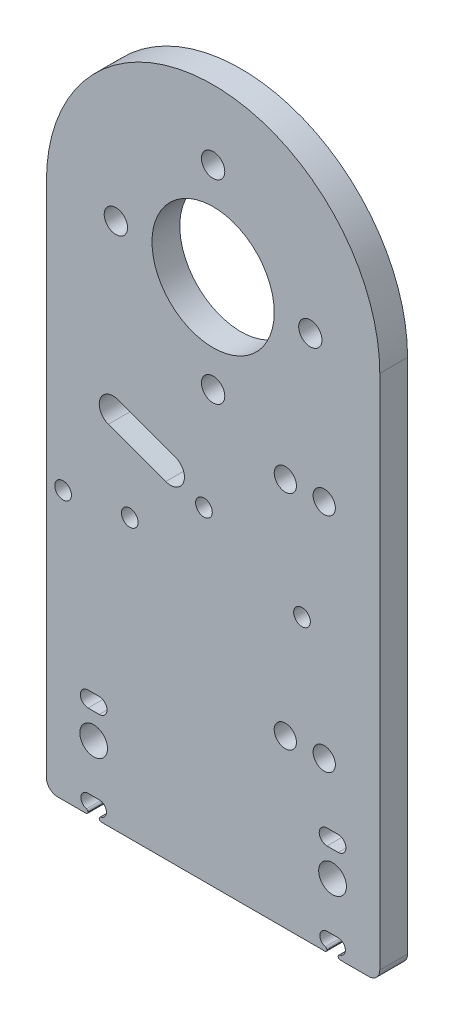
SolidWorks part; units mm, degrees
material "6061 Alloy"
ref_plane "Front Plane" through (0, 0, 0) normal (0, 0, 1) x (1, 0, 0)
ref_plane "Top Plane" through (0, 0, 0) normal (0, 1, 0) x (1, 0, 0)
ref_plane "Right Plane" through (0, 0, 0) normal (1, 0, 0) x (0, 0, -1)
sketch "Sketch1" plane through (0, 0, 0) normal (0, 0, 1) x (1, 0, 0)
  line L0 (20.5, -29.5) -> (22.5, -29.5) construction
  line L1 (-30, -47.5) -> (-22.5, -47.5)
  line L2 (-30, -47.5) -> (-30, 47.5)
  line L4 (30, -47.5) -> (30, 47.5)
  line L5 (0, 47.5) -> (0, -47.5) construction
  line L6 (-30, 0) -> (30, 0) construction
  line L11 (0, 6.5) -> (0, -24.5) construction
  line L12 (20.5, -28.1) -> (22.5, -28.1)
  line L13 (20.5, -30.9) -> (22.5, -30.9)
  line L14 (20.5, -45.5) -> (22.5, -45.5) construction
  line L15 (20.5, -44.2) -> (22.5, -44.2)
  line L17 (-20.5, -45.5) -> (-22.5, -45.5) construction
  line L18 (-20.5, -44.2) -> (-22.5, -44.2)
  line L20 (-20.5, -29.5) -> (-22.5, -29.5) construction
  line L21 (-20.5, -28.1) -> (-22.5, -28.1)
  line L22 (-20.5, -30.9) -> (-22.5, -30.9)
  line L23 (20.5, -46.8) -> (20.5, -47.5)
  line L28 (0, 71.5) -> (0, 30) construction
  line L29 (-17.5, 47.5) -> (17.5, 47.5) construction
  line L30 (22.5, -46.8) -> (22.5, -47.5)
  line L31 (-22.5, -46.8) -> (-22.5, -47.5)
  line L32 (-20.5, -46.8) -> (-20.5, -47.5)
  line L33 (-20.5, -47.5) -> (20.5, -47.5)
  line L34 (22.5, -47.5) -> (30, -47.5)
  circle A6 centre (0, 47.5) radius 11
  circle A7 centre (21.5, -35.5) radius 2.5
  arc A8 (20.5, -28.1) -> (20.5, -30.9) centre (20.5, -29.5) ccw
  arc A9 (22.5, -30.9) -> (22.5, -28.1) centre (22.5, -29.5) ccw
  arc A10 (20.5, -44.2) -> (20.5, -46.8) centre (20.5, -45.5) ccw
  arc A11 (22.5, -46.8) -> (22.5, -44.2) centre (22.5, -45.5) ccw
  circle A12 centre (-21.5, -35.5) radius 2.5
  arc A13 (-20.5, -44.2) -> (-20.5, -46.8) centre (-20.5, -45.5) cw
  arc A14 (-22.5, -46.8) -> (-22.5, -44.2) centre (-22.5, -45.5) cw
  arc A15 (-20.5, -28.1) -> (-20.5, -30.9) centre (-20.5, -29.5) cw
  arc A16 (-22.5, -30.9) -> (-22.5, -28.1) centre (-22.5, -29.5) cw
  circle A17 centre (0, 30) radius 2.1
  circle A18 centre (-17.5, 47.5) radius 2.1
  circle A19 centre (0, 65) radius 2.1
  circle A20 centre (17.5, 47.5) radius 2.1
  circle A21 centre (0, 47.5) radius 17.5 construction
  arc A22 (30, 47.5) -> (-30, 47.5) centre (0, 47.5) ccw
  circle A25 centre (-27, 0.7796) radius 1.5
  circle A26 centre (-1.6503, 10.7796) radius 1.5
  circle A27 centre (16, 2.5294) radius 1.5
  circle A28 centre (-15, 2.5294) radius 1.5
  point P0 (0, 0)
  point P8 (21.5, -29.5)
  point P16 (21.5, -45.5)
  point P26 (-21.5, -45.5)
  point P33 (-21.5, -29.5)
  dimension "D4" = 2
  dimension "D5" = 10
  dimension "D8" = 22
  dimension "D3" = 5
  dimension "D7" = 1.3
  dimension "D12" = 1.4
  dimension "D16" = 4.2
  dimension "D17" = 1.3
  dimension "D18" = 3
  dimension "D19" = 3
  dimension "D20" = 3
  dimension "D21" = 19.4833
  dimension "D22" = 8.2502
  dimension "D23" = 14
  dimension "D1" = 60
  dimension "D2" = 95
  dimension "D6" = 2
  dimension "D9" = 6
  dimension "D10" = 2
  dimension "D11" = 2
  dimension "D13" = 8.5
  dimension "D14" = 24
  dimension "D15" = 17.5
extrude "Boss-Extrude1" add sketch "Sketch1" along normal mid plane 5
sketch "Sketch2" plane through (0, 0, -2.5) normal (0, 0, -1) x (-1, 0, 0)
  line L0 (8.5184, 11.3885) -> (18.8551, 15.1508) construction
  line L1 (6.8083, 16.087) -> (17.1449, 19.8492) construction
  line L2 (8.5184, 11.3885) -> (18.8551, 15.1508)
  line L3 (6.8083, 16.087) -> (17.1449, 19.8492)
  arc A0 (6.8083, 16.087) -> (8.5184, 11.3885) centre (7.6634, 13.7378) ccw construction
  arc A1 (18.8551, 15.1508) -> (17.1449, 19.8492) centre (18, 17.5) ccw construction
  arc A2 (6.8083, 16.087) -> (8.5184, 11.3885) centre (7.6634, 13.7378) ccw
  arc A3 (18.8551, 15.1508) -> (17.1449, 19.8492) centre (18, 17.5) ccw
extrude "Cut-Extrude1" cut sketch "Sketch2" against normal through all
sketch "Sketch3" plane through (0, 0, 2.5) normal (0, 0, 1) x (1, 0, 0)
  line L0 (30, -47.5) -> (30, 47.5) construction
  line L1 (-30, -47.5) -> (-22.5, -47.5) construction
  circle A0 centre (13, -17.5) radius 2
  circle A1 centre (20, -17.5) radius 2
  circle A2 centre (13, 22.5) radius 2
  circle A3 centre (20, 22.5) radius 2
  dimension "D1" = 4
  dimension "D2" = 7
  dimension "D3" = 10
  dimension "D4" = 30
  dimension "D5" = 2
extrude "Cut-Extrude2" cut sketch "Sketch3" against normal through all
fillet "Fillet1" radius 0.4 8 edges at (22.5, -47.5, 0) (22.5, -46.8, 0) (20.5, -47.5, 0) (20.5, -46.8, 0) (-20.5, -46.8, 0) (-20.5, -47.5, 0) (-22.5, -47.5, 0) (-22.5, -46.8, 0)
fillet "Fillet2" radius 2 2 edges at (30, -47.5, 0) (-30, -47.5, 0)
